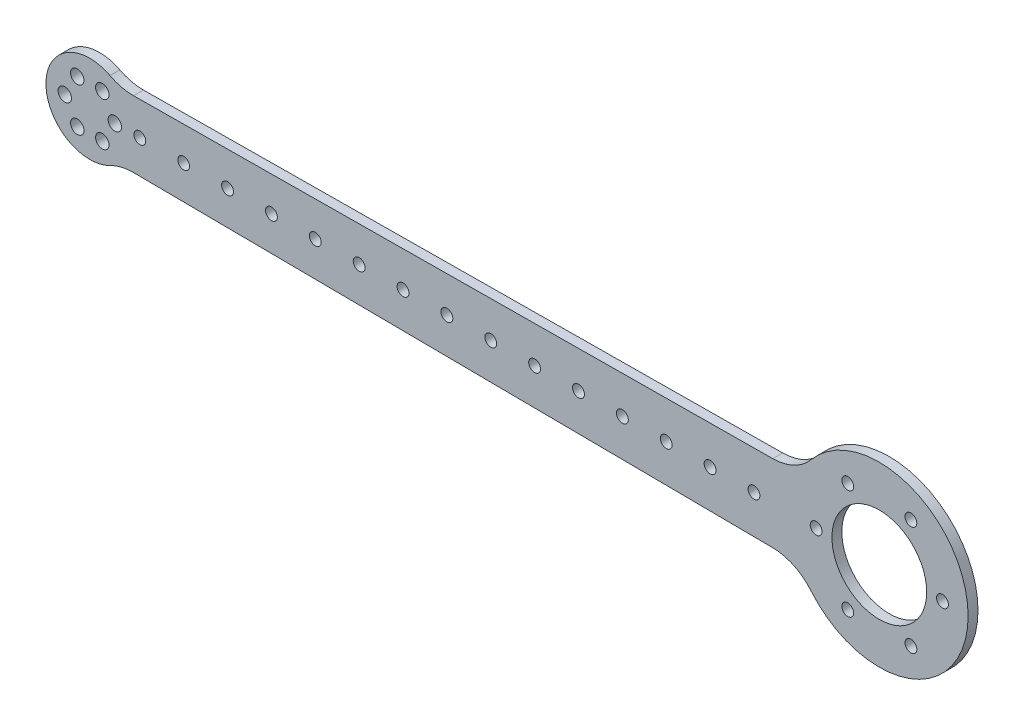
SolidWorks part; units mm, degrees
material "Hexcel AS4C (3000 Filaments)"
ref_plane "Front Plane" through (0, 0, 0) normal (0, 0, 1) x (1, 0, 0)
ref_plane "Top Plane" through (0, 0, 0) normal (0, 1, 0) x (1, 0, 0)
ref_plane "Right Plane" through (0, 0, 0) normal (1, 0, 0) x (0, 0, -1)
sketch "Sketch1" plane through (0, 0, 0) normal (0, 0, 1) x (1, 0, 0)
  line L0 (-100, 0) -> (100, 0) construction
  line L1 (-88.9892, 1.5) -> (77.6857, 2.8851)
  line L2 (-92.7234, 8.3988) -> (79.762, 9.8322)
  line L3 (-88.9892, -1.5) -> (77.6857, -2.8851)
  line L4 (-92.7234, -8.3988) -> (79.762, -9.8322)
  line L5 (-100, 0) -> (-100.0693, -8.3377) construction
  line L6 (-100.0693, -8.3377) -> (-92.7234, -8.3988) construction
  line L7 (-92.7234, 8.3988) -> (-100.0693, 8.3377) construction
  line L8 (-100.0693, 8.3377) -> (-100, 0) construction
  line L9 (-88.9892, 1.5) -> (-88.9892, -1.5)
  line L10 (100, 0) -> (99.9169, -9.9997) construction
  line L11 (99.9169, -9.9997) -> (79.762, -9.8322) construction
  line L12 (79.762, 9.8322) -> (99.9169, 9.9997) construction
  line L13 (99.9169, 9.9997) -> (100, 0) construction
  circle A0 centre (-100, 0) radius 11.1125 construction
  circle A1 centre (100, 0) radius 22.5 construction
  arc A2 (79.762, 9.8322) -> (79.762, -9.8322) centre (100, 0) cw
  arc A3 (77.6857, 2.8851) -> (77.6857, -2.8851) centre (100, 0) ccw
  arc A4 (-92.7234, 8.3988) -> (-92.7234, -8.3988) centre (-100, 0) ccw
  point P4 (0, 0)
  point P23 (-88.9892, 0)
  dimension "D2" = 22.225
  dimension "D3" = 45
  dimension "D1" = 200
  dimension "D5" = 6.9296
  dimension "D6" = 10
  dimension "D7" = 6.9296
  dimension "D4" = 10
  dimension "D8" = 3
extrude "Boss-Extrude1" add sketch "Sketch1" along normal mid plane 2.5
fillet "Fillet1" radius 12.7 4 edges at (79.762, 9.8322, 0) (79.762, -9.8322, 0) (-92.7234, -8.3988, 0) (-92.7234, 8.3988, 0)
sketch "Sketch2" plane through (0, 0, 0) normal (0, 0, 1) x (1, 0, 0)
  line L8 (-88.9892, 1.5) -> (-88.9892, -1.5) construction
  line L9 (-88.9892, -1.5) -> (77.6857, -2.8851) construction
  line L10 (77.6857, 2.8851) -> (-88.9892, 1.5) construction
  line L12 (-88.9892, 1.5) -> (-88.9892, -1.5)
  line L13 (-88.9892, -1.5) -> (77.6857, -2.8851)
  line L14 (77.6857, 2.8851) -> (-88.9892, 1.5)
  arc A6 (77.6857, 2.8851) -> (77.6857, -2.8851) centre (100, 0) ccw construction
  arc A7 (77.6857, 2.8851) -> (77.6857, -2.8851) centre (100, 0) ccw
extrude "Boss-Extrude2" add sketch "Sketch2" along normal mid plane 2.5
ref_axis "Axis1" through (100, 0, 1.25) along (0, 0, -1)
ref_axis "Axis2" through (-100, 0, 1.25) along (0, 0, -1)
sketch "Sketch3" plane through (0, 0, 0) normal (0, 0, 1) x (1, 0, 0)
  circle A0 centre (100, 0) radius 12
  dimension "D1" = 24
extrude "Cut-Extrude1" cut sketch "Sketch3" against normal through all both and the other way through all
sketch "Sketch5" plane through (0, 0, 0) normal (0, 0, 1) x (1, 0, 0)
  line L0 (100, 0) -> (116, 0) construction
  circle A0 centre (116, 0) radius 1.5
  dimension "D2" = 3
  dimension "D1" = 16
extrude "Cut-Extrude2" cut sketch "Sketch5" against normal through all both and the other way through all
pattern_circular "CirPattern1" count 6 over 360 about axis through (100, 0, 1.25) along (0, 0, -1) of "Cut-Extrude2"
sketch "Sketch6" plane through (0, 0, 1.25) normal (0, 0, 1) x (1, 0, 0)
  line L0 (100, 0) -> (68.25, 0) construction
  line L1 (-100, 0) -> (-31.7625, 0) construction
  circle A0 centre (68.25, 0) radius 1.5
  circle A1 centre (57.1375, 0) radius 1.5
  circle A2 centre (46.025, 0) radius 1.5
  circle A3 centre (34.9125, 0) radius 1.5
  circle A4 centre (23.8, 0) radius 1.5
  circle A5 centre (12.6875, 0) radius 1.5
  circle A6 centre (1.575, 0) radius 1.5
  circle A7 centre (-9.5375, 0) radius 1.5
  circle A8 centre (-20.65, 0) radius 1.5
  circle A9 centre (-31.7625, 0) radius 1.5
  circle A10 centre (-42.875, 0) radius 1.5
  circle A11 centre (-53.9875, 0) radius 1.5
  circle A12 centre (-65.1, 0) radius 1.5
  circle A13 centre (-76.2125, 0) radius 1.5
  circle A14 centre (-87.325, 0) radius 1.5
  dimension "D1" = 3
  dimension "D2" = 31.75
  dimension "D4" = 11.1125
  dimension "D3" = 15
extrude "Cut-Extrude3" cut sketch "Sketch6" against normal through all both and the other way through all
sketch "Sketch8" plane through (0, 0, 0) normal (0, 0, 1) x (1, 0, 0)
  line L1 (-115, -25.4) -> (-85, -25.4)
  line L2 (-115, -25.4) -> (-115, 25.4)
  line L3 (-115, 25.4) -> (-85, 25.4)
  line L4 (-85, -25.4) -> (-85, 25.4)
  line L5 (-115, -25.4) -> (-85, 25.4) construction
  line L6 (-115, 25.4) -> (-85, -25.4) construction
  point P0 (-100, 0)
  dimension "D1" = 15
  dimension "D2" = 50.8
extrude "Cut-Extrude4" [suppressed] cut sketch "Sketch8" against normal through all both and the other way through all
fillet "Fillet2" [suppressed] radius 2.3813
sketch "Sketch10" [suppressed] plane through (0, 0, 1.25) normal (0, 0, 1) x (1, 0, 0)
  line L0 (-100, 0) -> (-81.825, 0) construction
  line L1 (-85, -4.7688) -> (-85, 4.7688) construction
  line L2 (-81.825, -4) -> (-69.125, -4) construction
  line L3 (-81.825, -4) -> (-81.825, 4) construction
  line L4 (-81.825, 4) -> (-69.125, 4) construction
  line L5 (-69.125, -4) -> (-69.125, 4) construction
  circle A0 centre (-81.825, 4) radius 1.5
  circle A1 centre (-69.125, 4) radius 1.5
  circle A2 centre (-69.125, -4) radius 1.5
  circle A3 centre (-81.825, -4) radius 1.5
  point P8 (-81.825, 0)
  dimension "D4" = 3
  dimension "D1" = 3.175
  dimension "D2" = 12.7
  dimension "D3" = 8
extrude "Cut-Extrude5" [suppressed] cut sketch "Sketch10" against normal through all both and the other way through all
sketch "Sketch11" plane through (0, 0, 0) normal (0, 0, -1) x (-1, 0, 0)
  line L0 (93.65, 0) -> (100, 0) construction
  point P4 (93.65, 0)
  dimension "D2" = 6.35
hole_wizard "M3 Clearance Hole1" positions "Sketch12" profile "Sketch13" hole size "M3" standard "ANSI Metric" end condition up to next
sketch "Sketch12" plane through (0, 0, -1.25) normal (0, 0, -1) x (-1, 0, 0)
  point P0 (93.65, 0)
sketch "Sketch13" plane through (-93.65, 0, -1.25) normal (1, 0, 0) x (0, 1, 0)
  line L0 (0, 0) -> (0, 2.501)
  line L1 (0, 2.501) -> (1.7, 2.501)
  line L2 (1.7, 2.501) -> (1.7, 0)
  line L5 (1.7, 0) -> (0, 0)
  line L11 (0, -6.35) -> (0, 107.95) construction
  dimension "Thru Hole Dia." = 3.4
  dimension "Thru Hole Depth" = 2.501
pattern_circular "CirPattern3" count 6 over 360 about axis through (-100, 0, 1.25) along (0, 0, -1) of "M3 Clearance Hole1" reverse direction yes
equation "\"length\"= 200mm"
equation "\"D1@Sketch1\"=\"length\""
equation "\"Flange_Pulle\"= 45mm"
equation "\"D3@Sketch1\"=\"Flange_Pulle\""
equation "\"C_Upper\"= 10mm"
equation "\"Upper_Thickness\"= 5.5mm * ( 2 ^ ( 1 / 3 ) )"
equation "\"D5@Sketch1\"=\"Upper_Thickness\""
equation "\"C_Lower\"= 10mm"
equation "\"D6@Sketch1\"=\"C_Lower\""
equation "\"Lower_Thickness\" = \"Upper_Thickness\""
equation "\"D7@Sketch1\"=\"Lower_Thickness\""
equation "\"Foot_Diameter\"=0.875"
equation "\"D2@Sketch1\"=\"Foot_Diameter\""
equation "\"Thicknes\"= 2.5mm"
equation "\"D1@Boss-Extrude1\"=\"Thicknes\""
equation "\"D1@Boss-Extrude2\"=\"Thicknes\""
equation "\"D4@Sketch1\"=\"C_Upper\""
equation "\"m3_clearance\"= 3mm"
equation "\"screw_center_offset\"= 16mm"
equation "\"D2@Sketch5\"=\"m3_clearance\""
equation "\"D1@Sketch5\"=\"screw_center_offset\""
equation "\"D1@Sketch6\"=\"m3_clearance\""
equation "\"I_center_hole_spacing\"=0.4375"
equation "\"D4@Sketch6\"=\"I_center_hole_spacing\""
